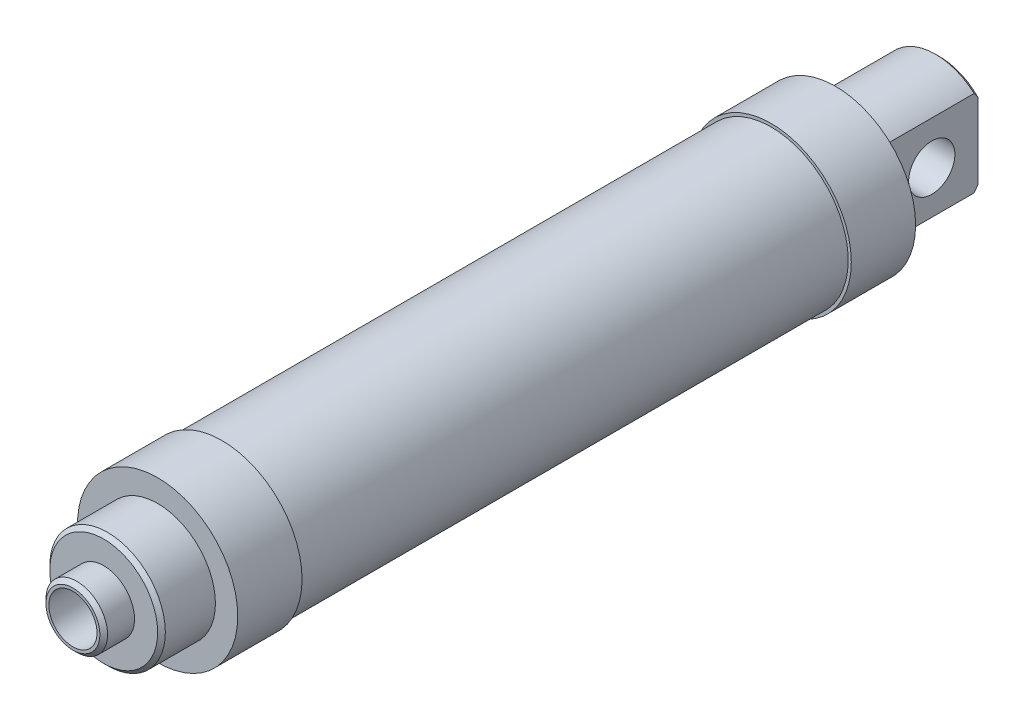
SolidWorks part; units mm, degrees
ref_plane "Plan de face" through (0, 0, 0) normal (0, 0, 1) x (1, 0, 0)
ref_plane "Plan de dessus" through (0, 0, 0) normal (0, 1, 0) x (1, 0, 0)
ref_plane "Plan de droite" through (0, 0, 0) normal (1, 0, 0) x (0, 0, -1)
sketch "Esquisse1" plane through (0, 0, 0) normal (0, 0, 1) x (1, 0, 0)
  circle A0 centre (0, 0) radius 20
  dimension "D1" = 40
extrude "Boss.-Extru.1" add sketch "Esquisse1" along normal blind 142.6
sketch "Esquisse2" plane through (0, 0, 142.6) normal (0, 0, 1) x (1, 0, 0)
  circle A0 centre (0, 0) radius 20.8
  dimension "D1" = 41.6
extrude "Boss.-Extru.2" add sketch "Esquisse2" along normal blind 16.7
extrude "Boss.-Extru.5" add sketch "Esquisse2<3>" against normal blind 16.7 from offset 142.6 offset against normal yes
sketch "Esquisse2<3>" plane through (0, 0, 142.6) normal (0, 0, 1) x (1, 0, 0) same geometry as "Esquisse2"
sketch "Esquisse3" plane through (0, 0, -16.7) normal (0, 0, -1) x (-1, 0, 0)
  circle A0 centre (0, 0) radius 15
  dimension "D1" = 30
extrude "Boss.-Extru.6" add sketch "Esquisse3" along normal blind 27
sketch "Esquisse4" plane through (0, 0, -43.7) normal (0, 0, -1) x (-1, 0, 0)
  line L0 (0, -15) -> (0, 15) construction
  line L1 (-10, -15) -> (0, -15) construction
  line L2 (-10, 15) -> (-16, 15)
  line L3 (-10, 15) -> (-10, -15)
  line L4 (-10, -15) -> (-16, -15)
  line L5 (-16, 15) -> (-16, -15)
  line L6 (0, 15) -> (-10, 15) construction
  line L7 (16, 15) -> (16, -15)
  line L8 (10, -15) -> (16, -15)
  line L9 (10, 15) -> (10, -15)
  line L10 (10, 15) -> (16, 15)
  circle A0 centre (0, 0) radius 15 construction
  circle A1 centre (0, 0) radius 15 construction
  dimension "D1" = 20
  dimension "D2" = 6
extrude "Enlèv. mat.-Extru.1" cut sketch "Esquisse4" against normal blind 26
sketch "Esquisse5" plane through (10, 0, 0) normal (1, 0, 0) x (0, 0, -1)
  line L0 (43.7, 0) -> (31.7, 0) construction
  line L1 (43.7, -11.1803) -> (43.7, 11.1803) construction
  line L2 (16.7, -15) -> (16.7, 15) construction
  circle A0 centre (31.7, 0) radius 6
  dimension "D1" = 12
  dimension "D2" = 15
extrude "Enlèv. mat.-Extru.2" cut sketch "Esquisse5" against normal through all
chamfer "Chanfrein1" distance 1 angle 45 2 edges at (0, 15, -43.7) (0, -15, -43.7)
sketch "Esquisse6" plane through (0, 0, 159.3) normal (0, 0, 1) x (1, 0, 0)
  circle A0 centre (0, 0) radius 15
  dimension "D1" = 30
extrude "Boss.-Extru.7" add sketch "Esquisse6" along normal blind 14
sketch "Esquisse7" plane through (0, 0, 173.3) normal (0, 0, 1) x (1, 0, 0)
  circle A0 centre (0, 0) radius 8
  dimension "D1" = 16
extrude "Boss.-Extru.8" add sketch "Esquisse7" along normal blind 8
chamfer "Chanfrein3" distance 1 angle 45 2 edges at (8, 0, 181.3) (15, 0, 173.3)
sketch "Esquisse9" plane through (0, 0, 181.3) normal (0, 0, 1) x (1, 0, 0)
  circle A0 centre (0, 0) radius 6.25
  dimension "D1" = 12.5
extrude "Enlèv. mat.-Extru.3" cut sketch "Esquisse9" against normal blind 100
